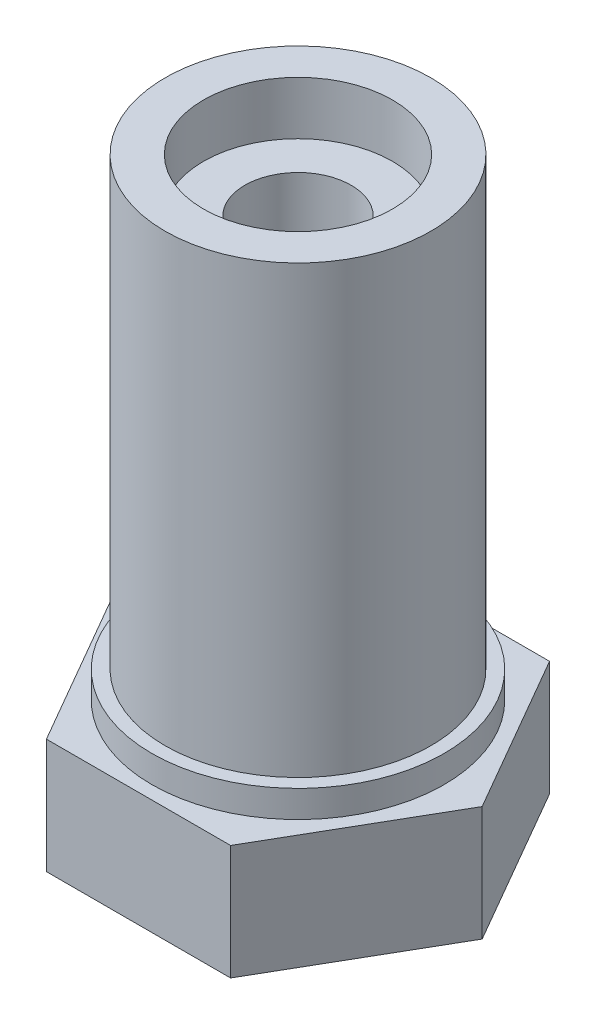
SolidWorks part; units mm, degrees
ref_plane "Front Plane" through (0, 0, 0) normal (0, 0, 1) x (1, 0, 0)
ref_plane "Top Plane" through (0, 0, 0) normal (0, 1, 0) x (1, 0, 0)
ref_plane "Right Plane" through (0, 0, 0) normal (1, 0, 0) x (0, 0, -1)
sketch "Sketch1" plane through (0, 0, 0) normal (0, 1, 0) x (1, 0, 0)
  line L1 (3.4641, 6) -> (-3.4641, 6)
  line L2 (-3.4641, 6) -> (-6.9282, 0)
  line L3 (-6.9282, 0) -> (-3.4641, -6)
  line L4 (-3.4641, -6) -> (3.4641, -6)
  line L5 (3.4641, -6) -> (6.9282, 0)
  line L6 (6.9282, 0) -> (3.4641, 6)
  circle A0 centre (0, 0) radius 6 construction
  dimension "D1" = 12
extrude "Boss-Extrude1" add sketch "Sketch1" along normal blind 4.318
sketch "Sketch2" plane through (0, 4.318, 0) normal (0, 1, 0) x (1, 0, 0)
  circle A0 centre (0, 0) radius 5
  circle A1 centre (0, 0) radius 5.5
  dimension "D1" = 11
  dimension "D2" = 10
extrude "Boss-Extrude2" add sketch "Sketch2" along normal blind 1.016
extrude "Boss-Extrude3" add sketch "Sketch2<2>" along normal blind 17.78 contours A0 region at (0, 4.318, 0)
sketch "Sketch2<2>" plane through (0, 4.318, 0) normal (0, 1, 0) x (1, 0, 0) same geometry as "Sketch2"
sketch "Sketch4" plane through (0, 22.098, 0) normal (0, 1, 0) x (1, 0, 0)
  circle A0 centre (0, 0) radius 3.556
  circle A1 centre (0, 0) radius 2
  dimension "D1" = 7.112
  dimension "D2" = 4
extrude "Cut-Extrude2" cut sketch "Sketch4" against normal through all contours A1 region at (0, 22.098, 0)
extrude "Cut-Extrude3" cut sketch "Sketch4<3>" against normal blind 2
sketch "Sketch4<3>" plane through (0, 22.098, 0) normal (0, 1, 0) x (1, 0, 0) same geometry as "Sketch4"
